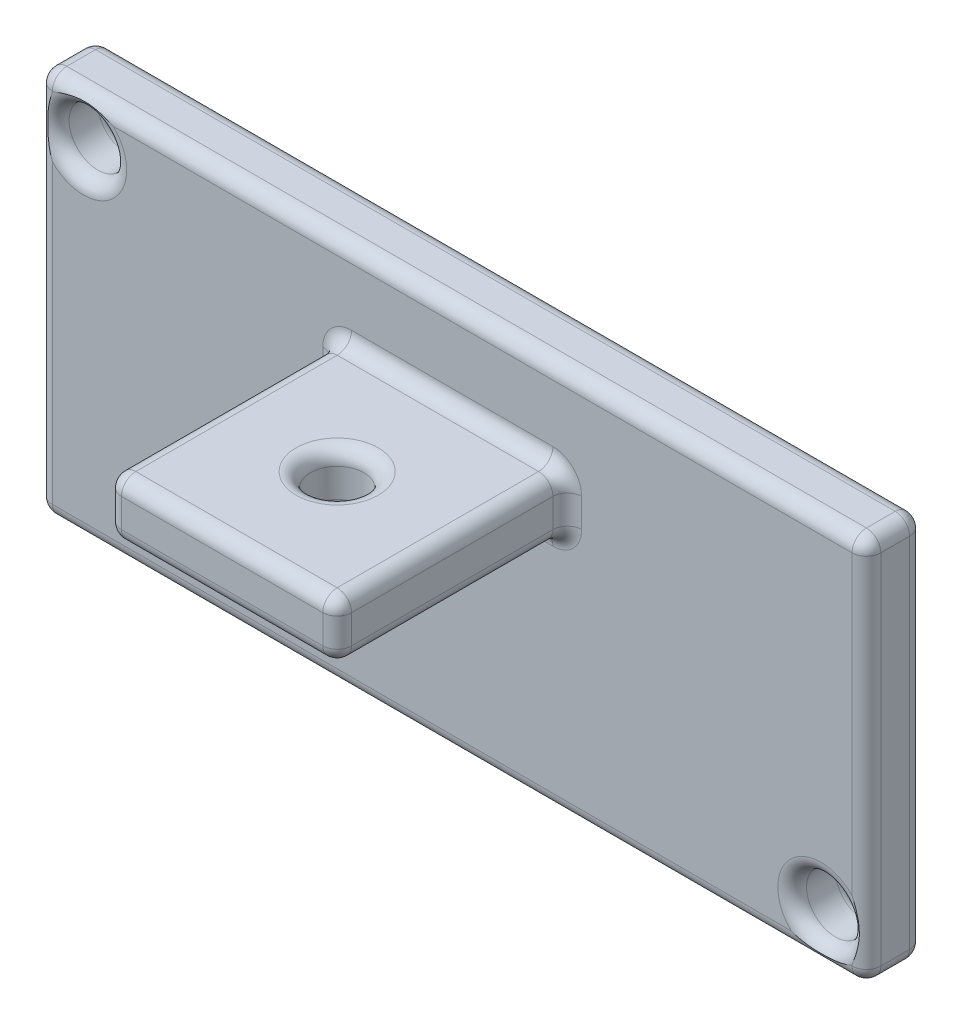
SolidWorks part; units mm, degrees
ref_plane "Front Plane" through (0, 0, 0) normal (0, 0, 1) x (1, 0, 0)
ref_plane "Top Plane" through (0, 0, 0) normal (0, 1, 0) x (1, 0, 0)
ref_plane "Right Plane" through (0, 0, 0) normal (1, 0, 0) x (0, 0, -1)
sketch "Sketch3" plane through (0, 0, 0) normal (0, 0, 1) x (1, 0, 0)
  line L1 (-22.86, -10.668) -> (22.86, -10.668)
  line L2 (-22.86, -10.668) -> (-22.86, 10.668)
  line L3 (-22.86, 10.668) -> (22.86, 10.668)
  line L4 (22.86, -10.668) -> (22.86, 10.668)
  line L5 (-22.86, -10.668) -> (22.86, 10.668) construction
  line L6 (-22.86, 10.668) -> (22.86, -10.668) construction
  point P0 (0, 0)
  dimension "D1" = 45.72
  dimension "D2" = 21.336
extrude "Boss-Extrude1" add sketch "Sketch3" along normal blind 3.175
sketch "Sketch4" plane through (0, 0, 3.175) normal (0, 0, 1) x (1, 0, 0)
  line L5 (20.35, -8.15) -> (-20.35, -8.15) construction
  line L6 (20.35, -8.15) -> (20.35, 8.15) construction
  line L7 (20.35, 8.15) -> (-20.35, 8.15) construction
  line L8 (-20.35, -8.15) -> (-20.35, 8.15) construction
  line L9 (20.35, -8.15) -> (-20.35, 8.15) construction
  line L10 (20.35, 8.15) -> (-20.35, -8.15) construction
  circle A0 centre (-20.35, 8.15) radius 1.5875
  circle A1 centre (20.35, -8.15) radius 1.5875
  point P4 (0, 0)
  dimension "D1" = 3.175
  dimension "D2" = 3.175
  dimension "D3" = 40.7
  dimension "D4" = 16.3
extrude "Cut-Extrude1" cut sketch "Sketch4" against normal up to surface (3.175 mm away) up to face at (0, 0, 0)
sketch "Sketch6" plane through (0, 0, 3.175) normal (0, 0, 1) x (1, 0, 0)
  line L0 (0, 4.318) -> (0, 10.668) construction
  line L1 (-6.35, 2.7305) -> (6.35, 2.7305)
  line L2 (-6.35, 2.7305) -> (-6.35, 5.9055)
  line L3 (-6.35, 5.9055) -> (6.35, 5.9055)
  line L4 (6.35, 2.7305) -> (6.35, 5.9055)
  line L5 (-6.35, 2.7305) -> (6.35, 5.9055) construction
  line L6 (-6.35, 5.9055) -> (6.35, 2.7305) construction
  line L7 (22.86, 10.668) -> (-22.86, 10.668) construction
  point P0 (0, 4.318)
  dimension "D1" = 3.175
  dimension "D2" = 6.35
  dimension "D3" = 12.7
extrude "Boss-Extrude2" add sketch "Sketch6" along normal blind 12.7
sketch "Sketch7" plane through (0, 5.9055, 0) normal (0, 1, 0) x (1, 0, 0)
  line L0 (0, -9.525) -> (6.35, -9.525) construction
  line L2 (0, -9.525) -> (0, -15.875) construction
  line L3 (6.35, -15.875) -> (-6.35, -15.875) construction
  line L4 (6.35, -15.875) -> (6.35, -3.175) construction
  circle A0 centre (0, -9.525) radius 1.4732
  dimension "D1" = 2.9464
extrude "Cut-Extrude2" cut sketch "Sketch7" against normal up to surface (3.175 mm away) up to face at (0, 2.7305, 9.525)
fillet "Fillet1" radius 0.7937 30 edges at (-6.35, 5.9055, 9.525) (-6.35, 2.7305, 9.525) (0, 5.9055, 10.9982) (0, 2.7305, 10.9982) (6.35, 5.9055, 9.525) (6.35, 2.7305, 9.525) (0, 5.9055, 15.875) (0, 2.7305, 15.875) (0, 5.9055, 3.175) (0, 2.7305, 3.175) (-6.35, 4.318, 15.875) (-6.35, 4.318, 3.175) (6.35, 4.318, 15.875) (6.35, 4.318, 3.175) (18.7625, -8.15, 0) (-21.9375, 8.15, 0) (-22.86, -10.668, 1.5875) (-22.86, 0, 0) (0, 10.668, 0) (0, -10.668, 0) (22.86, 0, 0) (22.86, -10.668, 1.5875) (22.86, 10.668, 1.5875) (-22.86, 10.668, 1.5875) (0, -10.668, 3.175) (-22.86, 0, 3.175) (0, 10.668, 3.175) (22.86, 0, 3.175) (-18.7625, 8.15, 3.175) (21.9375, -8.15, 3.175)
